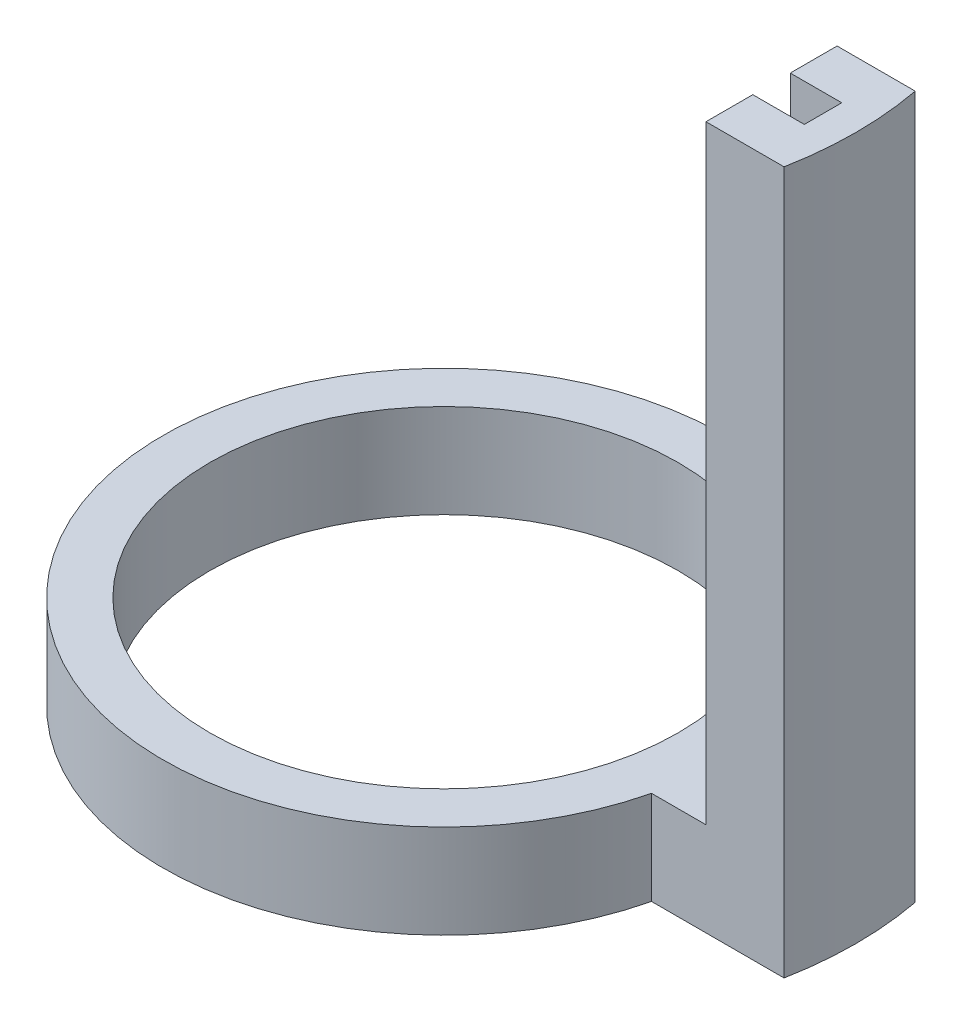
SolidWorks part; units mm, degrees
ref_plane "Front Plane" through (0, 0, 0) normal (0, 0, 1) x (1, 0, 0)
ref_plane "Top Plane" through (0, 0, 0) normal (0, 1, 0) x (1, 0, 0)
ref_plane "Right Plane" through (0, 0, 0) normal (1, 0, 0) x (0, 0, -1)
sketch "Sketch1" plane through (0, 0, 0) normal (0, 1, 0) x (1, 0, 0)
  line L0 (-8.0097, 0) -> (51.9903, 0)
  line L1 (51.9903, 0) -> (61.9471, 0)
  line L2 (61.9471, 0) -> (79.9471, 0)
  line L3 (61.9471, 0) -> (72.9471, 0)
  line L4 (61.9471, 0) -> (61.9471, 3.9787)
  line L5 (72.9471, 0) -> (72.9471, 3.9787)
  line L6 (61.9471, 3.9787) -> (72.9471, 3.9787)
  line L7 (61.9471, 0) -> (61.9471, -4.0221)
  line L8 (61.9471, 0) -> (72.9471, 0)
  line L9 (61.9471, -4.0221) -> (72.9471, -4.0221)
  line L10 (72.9471, 0) -> (72.9471, -4.0221)
  line L11 (78.6329, 13.9787) -> (50.3392, 13.9787)
  line L12 (50.3288, -14.0221) -> (78.6246, -14.0221)
  line L13 (61.9471, 3.9787) -> (51.8582, 3.9787)
  line L14 (61.9471, -4.0221) -> (51.8553, -4.0221)
  line L15 (61.9471, 3.9787) -> (61.9471, 13.9787)
  line L16 (61.9471, -4.0221) -> (61.9471, -14.0221)
  circle A0 centre (-8.0097, 0) radius 50
  circle A1 centre (-8.0097, 0) radius 60
  circle A2 centre (4.9471, 0) radius 75
  dimension "D1" = 100
  dimension "D2" = 120
  dimension "D3" = 10
  dimension "D5" = 150
  dimension "D4" = 10
  dimension "D6" = 18
  dimension "D7" = 11
extrude "Boss-Extrude1" add sketch "Sketch1" along normal blind 20 contours A1 A0 | A1 L13 L15 L11 | A1 L1 L4 L13 | A1 L14 L7 L1 | A1 L12 L16 L14 region at (50.2604, 0, 1.9553) region at (56.9466, 0, -1.9937) region at (56.9461, 0, 2.0156) region at (56.5857, 0, -9.0968) region at (56.5823, 0, 9.1407)
extrude "Boss-Extrude2" add sketch "Sketch1<4>" along normal blind 150 contours L2 A2 L11 L15 L6 L5 | L12 A2 L2 L10 L9 L16 region at (71.446, 0, -7.9681) region at (71.4513, 0, 7.9991)
sketch "Sketch1<4>" plane through (0, 0, 0) normal (0, 1, 0) x (1, 0, 0) same geometry as "Sketch1"
